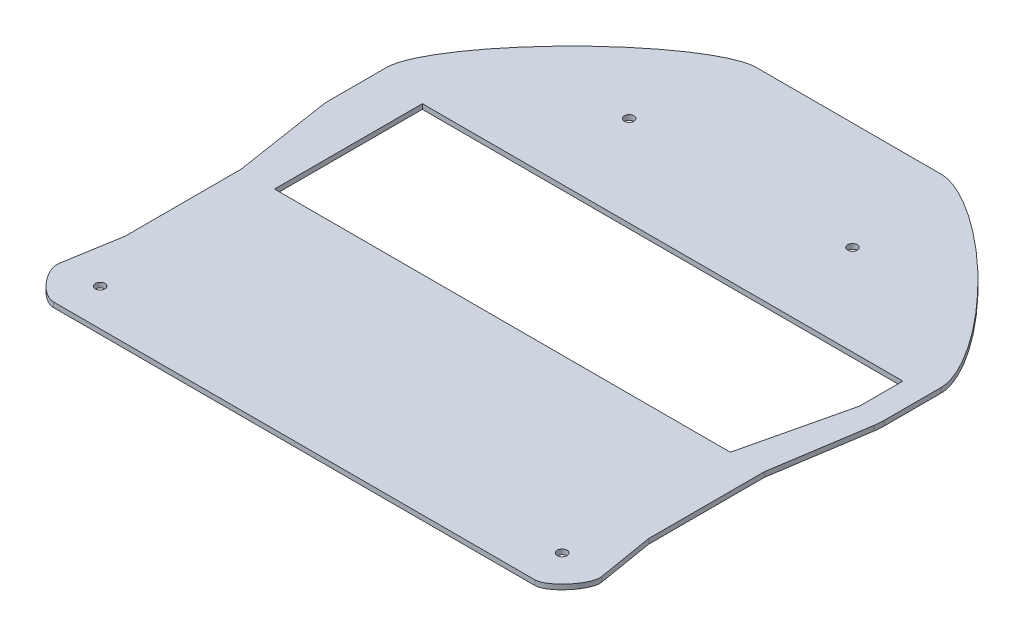
SolidWorks part; units mm, degrees
ref_plane "Front Plane" through (0, 0, 0) normal (0, 0, 1) x (1, 0, 0)
ref_plane "Top Plane" through (0, 0, 0) normal (0, 1, 0) x (1, 0, 0)
ref_plane "Right Plane" through (0, 0, 0) normal (1, 0, 0) x (0, 0, -1)
sketch "Sketch1" plane through (0, 0, 0) normal (0, 1, 0) x (1, 0, 0)
  line L0 (-90, 180) -> (-90, 0) construction
  line L1 (-180, 180) -> (0, 180)
  line L2 (-180, 180) -> (-180, 0)
  line L3 (-180, 0) -> (0, 0)
  line L4 (0, 180) -> (0, 0)
  line L5 (-180, 90) -> (0, 90) construction
  line L6 (-180, 30) -> (0, 30)
  line L7 (-130, 30) -> (-50, 30)
  line L8 (-130, 30) -> (-130, -30)
  line L9 (-130, -30) -> (-50, -30)
  line L10 (-50, 30) -> (-50, -30)
  line L11 (-130, 30) -> (-50, -30) construction
  line L12 (-130, -30) -> (-50, 30) construction
  dimension "D1" = 180
  dimension "D2" = 180
  dimension "D3" = 60
  dimension "D4" = 80
extrude "Boss-Extrude1" add sketch "Sketch1" along normal blind 1.6 contours L10 L3 L8 L9 | L2 L6 L4 L1 | L6 L10 L3 L4 | L8 L6 L2 L3 | L10 L6 L8 L3 region at (-90, 0, -105) region at (-155, 0, -15) region at (-25, 0, -15) region at (-90, 0, -15) region at (-90, 0, 15)
sketch "Sketch2" plane through (0, 1.6, 0) normal (0, 1, 0) x (1, 0, 0)
  line L0 (-180, 30) -> (0, 30)
  line L1 (-180, 180) -> (-180, 0) construction
  line L2 (0, 180) -> (0, 0) construction
  line L3 (-180, 180) -> (0, 180) construction
  line L4 (-90, 180) -> (-90, -30) construction
  line L5 (-130, -30) -> (-50, -30) construction
  dimension "D1" = 150
sketch "Sketch3" plane through (0, 1.6, 0) normal (0, 1, 0) x (1, 0, 0)
  line L0 (-180, 122) -> (0, 122)
  line L1 (-180, 180) -> (-180, 0) construction
  line L2 (0, 180) -> (0, 0) construction
  line L3 (-180, 30) -> (0, 30) construction
  dimension "D1" = 92
sketch "Sketch5" plane through (0, 1.6, 0) normal (0, 1, 0) x (1, 0, 0)
  line L0 (-114, 180) -> (-114, -30)
  line L1 (-180, 180) -> (0, 180) construction
  line L2 (-130, -30) -> (-50, -30) construction
  line L3 (-90, 180) -> (-90, -30) construction
  dimension "D1" = 24
fillet "Fillet1" radius 60 2 edges at (0, 0.8, -180) (-180, 0.8, -180) conic rho 0.2
sketch "Sketch6" plane through (0, 1.6, 0) normal (0, 1, 0) x (1, 0, 0)
  line L0 (-50, 0) -> (-130, 0)
  line L1 (-130, 0) -> (-130, -30)
  line L2 (-130, -30) -> (-50, -30)
  line L3 (-50, -30) -> (-50, 0)
  line L4 (-180, 0) -> (-175, 30.1113)
  line L5 (-175, 30.1113) -> (-175, 67.7113)
  line L6 (-175, 67.7113) -> (-180, 100)
  line L7 (-180, 120) -> (-180, 0) construction
  line L8 (-90, 180) -> (-90, -30) construction
  line L10 (-90, 180) -> (-90, 0) construction
  line L11 (0, 0) -> (-5, 30.1113)
  line L12 (-5, 30.1113) -> (-5, 67.7113)
  line L13 (-5, 67.7113) -> (0, 100)
  line M3 (0, 0) -> (0, 120)
  line M7 (-180, 120) -> (-180, 0)
  line M9 (-130, 0) -> (-130, -30)
  line M10 (-130, -30) -> (-50, -30)
  line M11 (-50, -30) -> (-50, 0)
  dimension "D1" = 37.6
  dimension "D2" = 85
  dimension "D3" = 100
extrude "Cut-Extrude1" cut sketch "Sketch6" against normal blind 10 contours L0 M11 M9 M10 | L5 L6 L4 M7 | L13 L12 L11 M3 region at (-90, 1.6, 15) region at (-177.8779, 1.6, -49.5379) region at (-2.1221, 1.6, -49.5379)
fillet "Fillet2" radius 10 2 edges at (-180, 0.8, 0) (0, 0.8, 0) conic rho 0.25
fillet "Fillet3" radius 20 2 edges at (-180, 0.8, -100) (0, 0.8, -100)
sketch "Sketch9" plane through (0, 1.6, 0) normal (0, 1, 0) x (1, 0, 0)
  line L0 (-175, 67.6) -> (-5, 67.6) construction
  line L1 (-175, 30.1113) -> (-175, 67.7113) construction
  line L2 (-5, 30.1113) -> (-5, 67.7113) construction
  line L3 (-180, 30) -> (0, 30) construction
  line L4 (-180, 115.6) -> (0, 115.6) construction
  line L5 (-180, 120) -> (-180, 101.5394) construction
  line L6 (0, 120) -> (0, 101.5394) construction
  line L7 (-16, 115.6) -> (-16, 67.6) construction
  line L8 (-90, 180) -> (-90, -30) construction
  line L9 (-164, 115.6) -> (-164, 67.6)
  line L10 (0, 101.5394) -> (-16, 101.5394) construction
  line L11 (-8, 101.5394) -> (-8, 115.6)
  line L12 (-164, 115.6) -> (-8, 115.6)
  line L14 (-16, 67.6) -> (-164, 67.6)
  line L16 (-8, 101.5394) -> (-16, 67.6)
  dimension "D1" = 37.6
  dimension "D2" = 48
  dimension "D3" = 74
  dimension "D4" = 74
extrude "Cut-Extrude3" cut sketch "Sketch9" against normal up to next
sketch "Sketch11" plane through (0, 1.6, 0) normal (0, 1, 0) x (1, 0, 0)
  line L0 (-168.2026, 0) -> (-11.7974, 0) construction
  line L1 (-175, 30.1113) -> (-175, 67.7113) construction
  line L2 (-114, 180) -> (-114, -30) construction
  line L3 (-180, 122) -> (0, 122) construction
  line L4 (-90, 180) -> (-90, 0) construction
  circle A0 centre (-165, 12) radius 1.55
  circle A1 centre (-126.25, 145) radius 1.55
  circle A2 centre (-15, 12) radius 1.55
  circle A3 centre (-53.75, 145) radius 1.55
  dimension "D1" = 3.1
  dimension "D2" = 12
  dimension "D4" = 3.1
  dimension "D5" = 12.25
  dimension "D6" = 23
  dimension "D3" = 10
extrude "Cut-Extrude5" cut sketch "Sketch11" against normal up to next
